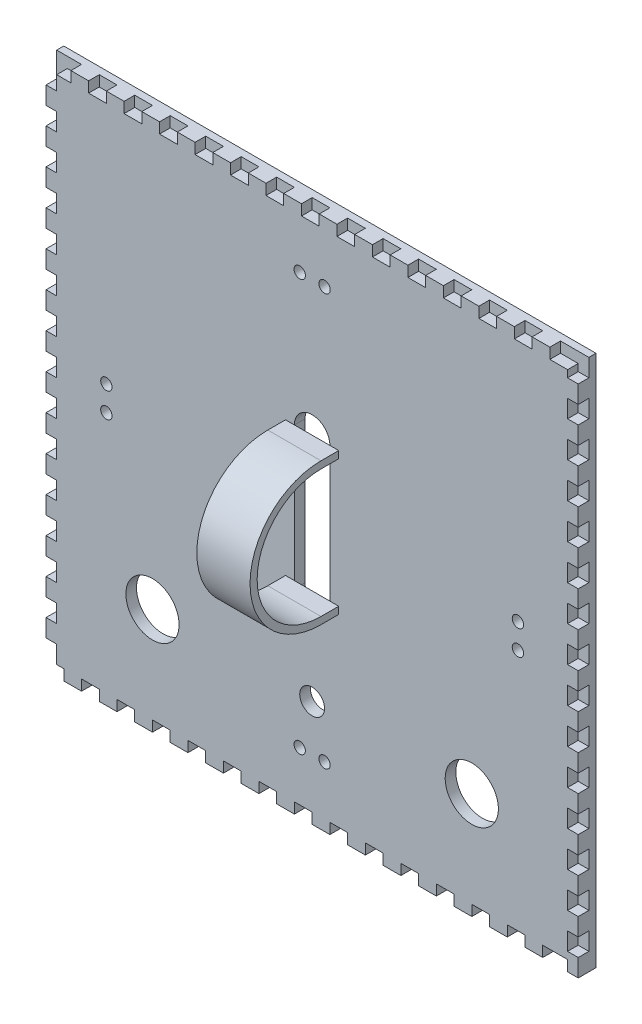
SolidWorks part; units mm, degrees
ref_plane "Front Plane" through (0, 0, 0) normal (0, 0, 1) x (1, 0, 0)
ref_plane "Top Plane" through (0, 0, 0) normal (0, 1, 0) x (1, 0, 0)
ref_plane "Right Plane" through (0, 0, 0) normal (1, 0, 0) x (0, 0, -1)
sketch "Sketch1" plane through (0, 0, 0) normal (0, 0, 1) x (1, 0, 0)
  line L1 (-75, 75) -> (75, 75)
  line L2 (-75, 75) -> (-75, -75)
  line L3 (-75, -75) -> (75, -75)
  line L4 (75, 75) -> (75, -75)
  line L5 (-75, 75) -> (75, -75) construction
  line L6 (-75, -75) -> (75, 75) construction
  point P0 (0, 0)
  dimension "D1" = 150
  dimension "D2" = 150
extrude "Boss-Extrude1" add sketch "Sketch1" along normal blind 5
sketch "Sketch2" plane through (0, 0, 0) normal (0, 0, -1) x (-1, 0, 0)
  line L1 (-65, 65) -> (65, 65)
  line L2 (-65, 65) -> (-65, -65)
  line L3 (-65, -65) -> (65, -65)
  line L4 (65, 65) -> (65, -65)
  line L5 (-65, 65) -> (65, -65) construction
  line L6 (-65, -65) -> (65, 65) construction
  point P0 (0, 0)
  dimension "D1" = 130
  dimension "D2" = 130
extrude "Cut-Extrude1" cut sketch "Sketch2" against normal blind 2
sketch "Sketch3" plane through (0, 0, 2) normal (0, 0, -1) x (-1, 0, 0)
  line L0 (0, 20) -> (0, -20) construction
  line L1 (5, 20) -> (5, -20)
  line L2 (-5, 20) -> (-5, -20)
  arc A0 (5, 20) -> (-5, 20) centre (0, 20) ccw
  arc A1 (-5, -20) -> (5, -20) centre (0, -20) ccw
  point P3 (0, 0)
  dimension "D2" = 5
  dimension "D1" = 40
extrude "Cut-Extrude2" cut sketch "Sketch3" against normal through all
sketch "Sketch4" plane through (75, 0, 0) normal (1, 0, 0) x (0, 0, -1)
  line L1 (-5, 75) -> (-2, 75)
  line L2 (-5, 75) -> (-5, 70)
  line L3 (-5, 70) -> (-2, 70)
  line L4 (-2, 75) -> (-2, 70)
  dimension "D1" = 3
  dimension "D2" = 5
extrude "Cut-Extrude3" cut sketch "Sketch4" against normal blind 3
pattern_linear "LPattern1" count 15 spacing 10 along (0, -1, 0) of "Cut-Extrude3"
sketch "Sketch5" plane through (0, -75, 0) normal (0, -1, 0) x (1, 0, 0)
  line L0 (-75, 5) -> (75, 5) construction
  line L1 (72, 5) -> (65, 5)
  line L2 (72, 5) -> (72, 2)
  line L3 (72, 2) -> (65, 2)
  line L4 (65, 5) -> (65, 2)
  line L5 (75, 5) -> (75, 0) construction
  dimension "D1" = 3
  dimension "D2" = 3
  dimension "D3" = 7
extrude "Cut-Extrude4" cut sketch "Sketch5" against normal blind 3
sketch "Sketch6" plane through (0, -75, 0) normal (0, -1, 0) x (1, 0, 0)
  line L0 (-75, 5) -> (65, 5) construction
  line L1 (60, 5) -> (55, 5)
  line L2 (60, 5) -> (60, 2)
  line L3 (60, 2) -> (55, 2)
  line L4 (55, 5) -> (55, 2)
  line L5 (65, 5) -> (65, 2) construction
  dimension "D1" = 5
  dimension "D2" = 5
  dimension "D3" = 3
extrude "Cut-Extrude5" cut sketch "Sketch6" against normal blind 3
pattern_linear "LPattern2" count 14 spacing 10 along (-1, 0, 0) of "Cut-Extrude5"
sketch "Sketch7" plane through (0, 75, 0) normal (0, 1, 0) x (1, 0, 0)
  line L1 (72, -5) -> (67, -5)
  line L2 (72, -5) -> (72, -2)
  line L3 (72, -2) -> (67, -2)
  line L4 (67, -5) -> (67, -2)
  dimension "D1" = 3
  dimension "D2" = 5
extrude "Cut-Extrude6" cut sketch "Sketch7" against normal blind 3
pattern_linear "LPattern3" count 15 spacing 10 along (-1, 0, 0) of "Cut-Extrude6"
sketch "Sketch8" plane through (0, 75, 0) normal (0, 1, 0) x (1, 0, 0)
  line L1 (-73, -5) -> (-75, -5)
  line L2 (-73, -5) -> (-73, -2)
  line L3 (-73, -2) -> (-75, -2)
  line L4 (-75, -5) -> (-75, -2)
extrude "Cut-Extrude7" cut sketch "Sketch8" against normal blind 3
sketch "Sketch9" plane through (-75, 0, 0) normal (-1, 0, 0) x (0, 0, 1)
  line L1 (5, 72) -> (2, 72)
  line L2 (5, 72) -> (5, 68)
  line L3 (5, 68) -> (2, 68)
  line L4 (2, 72) -> (2, 68)
  dimension "D1" = 3
  dimension "D2" = 4
extrude "Cut-Extrude8" cut sketch "Sketch9" against normal blind 3
sketch "Sketch10" plane through (-75, 0, 0) normal (-1, 0, 0) x (0, 0, 1)
  line L0 (5, 68) -> (5, -72) construction
  line L1 (5, 63) -> (2, 63)
  line L2 (5, 63) -> (5, 58)
  line L3 (5, 58) -> (2, 58)
  line L4 (2, 63) -> (2, 58)
  line L5 (2, 68) -> (5, 68) construction
  dimension "D1" = 3
  dimension "D2" = 5
  dimension "D3" = 5
extrude "Cut-Extrude9" cut sketch "Sketch10" against normal blind 3
pattern_linear "LPattern4" count 14 spacing 10 along (0, -1, 0) of "Cut-Extrude9"
sketch "Sketch11" plane through (0, 0, 0) normal (0, 0, -1) x (-1, 0, 0)
  line L0 (-65, 65) -> (-65, -65) construction
  line L2 (-75, -75) -> (-75, 75) construction
  circle A0 centre (-58, 3.5) radius 1.6
  circle A1 centre (-58, -3.5) radius 1.6
  point P8 (-65, 0)
  dimension "D3" = 3.2
  dimension "D4" = 3.2
  dimension "D1" = 17
  dimension "D2" = 17
  dimension "D5" = 3.5
  dimension "D6" = 3.5
extrude "Cut-Extrude10" cut sketch "Sketch11" against normal blind 15
mirror "Mirror1" about plane through (0, 0, 0) normal (1, 0, 0) of "Cut-Extrude10"
sketch "Sketch12" plane through (0, 0, 0) normal (0, 0, -1) x (-1, 0, 0)
  line L1 (-65, -65) -> (65, -65) construction
  line L2 (75, -75) -> (-75, -75) construction
  circle A0 centre (3.5, -58) radius 1.6
  circle A1 centre (-3.5, -58) radius 1.6
  point P8 (0, -65)
  dimension "D2" = 3.2
  dimension "D3" = 3.2
  dimension "D1" = 17
  dimension "D4" = 17
  dimension "D5" = 3.5
  dimension "D6" = 3.5
extrude "Cut-Extrude11" cut sketch "Sketch12" against normal blind 15
mirror "Mirror2" about plane through (0, 0, 0) normal (0, 1, 0) of "Cut-Extrude11"
sketch "Sketch15" plane through (0, 0, 0) normal (1, 0, 0) x (0, 0, -1)
  line L0 (-5, 18) -> (-10, 18)
  line L1 (-5, 15) -> (-5, 20) construction
  line L2 (-10, -18) -> (-5, -18)
  line L3 (-5, -25) -> (-5, -20) construction
  line L4 (-5, 20) -> (-10, 20)
  line L5 (-10, -20) -> (-5, -20)
  line L6 (-5, 20) -> (-5, 18)
  line L7 (-5, -18) -> (-5, -20)
  arc A0 (-10, 18) -> (-10, -18) centre (-10, 0) ccw
  arc A1 (-10, 20) -> (-10, -20) centre (-10, 0) ccw
  dimension "D1" = 18
  dimension "D2" = 10
  dimension "D3" = 2
extrude "Boss-Extrude2" add sketch "Sketch15" along normal mid plane 15 separate body
sketch "Sketch16" plane through (0, 0, 2) normal (0, 0, -1) x (-1, 0, 0)
  line L0 (-65, -65) -> (65, -65) construction
  line L1 (-65, 65) -> (-65, -65) construction
  line L2 (65, -65) -> (65, 65) construction
  circle A0 centre (45, -45) radius 7.5
  circle A1 centre (-45, -45) radius 7.5
  circle A2 centre (0, -45) radius 3.5
  dimension "D1" = 15
  dimension "D2" = 15
  dimension "D6" = 7
  dimension "D3" = 20
  dimension "D4" = 20
  dimension "D5" = 20
extrude "Cut-Extrude12" cut sketch "Sketch16" against normal blind 10
